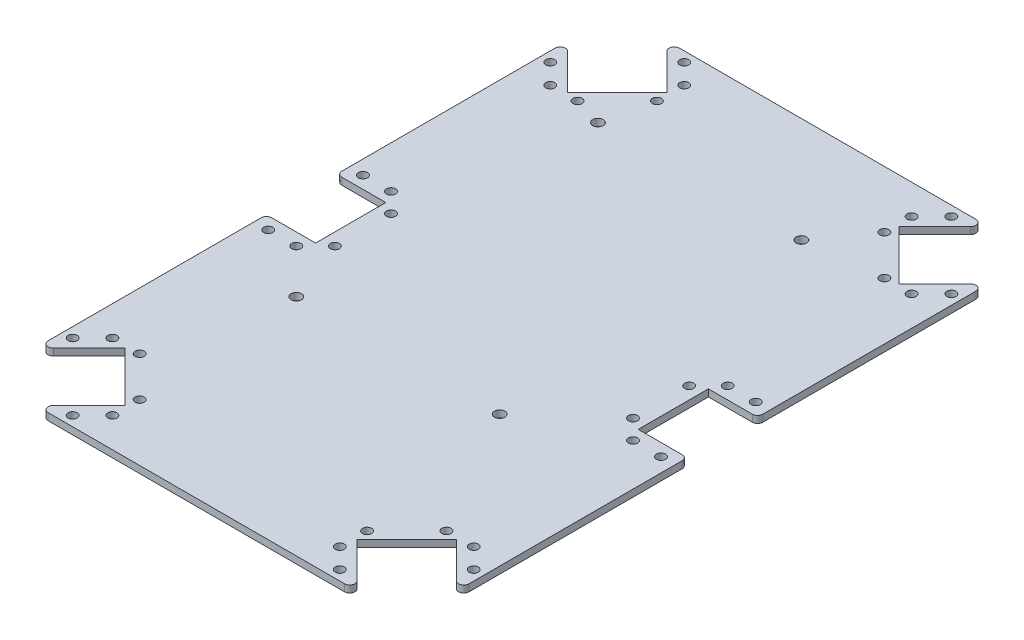
SolidWorks part; units mm, degrees
ref_plane "Front Plane" through (0, 0, 0) normal (0, 0, 1) x (1, 0, 0)
ref_plane "Top Plane" through (0, 0, 0) normal (0, 1, 0) x (1, 0, 0)
ref_plane "Right Plane" through (0, 0, 0) normal (1, 0, 0) x (0, 0, -1)
sketch "Sketch2" plane through (0, 0, 0) normal (0, 1, 0) x (1, 0, 0)
  line L0 (-60, 0) -> (60, 0) construction
  line L1 (-60, 90) -> (60, 90)
  line L2 (-60, 90) -> (-60, -90)
  line L3 (-60, -90) -> (60, -90)
  line L4 (60, 90) -> (60, -90)
  line L5 (60, 90) -> (0, 30) construction
  line L7 (0, 90) -> (0, -90) construction
  line L8 (32.4228, 73.7365) -> (28.5337, 77.6256) construction
  line L9 (28.5337, 77.6256) -> (32.4228, 81.5147) construction
  line L10 (32.4228, 81.5147) -> (38.0797, 87.1716) construction
  line L11 (38.0797, 87.1716) -> (40.9081, 90) construction
  circle A5 centre (32.4228, 73.7365) radius 1.3
  circle A6 centre (32.4228, 81.5147) radius 1.3
  circle A7 centre (38.0797, 87.1716) radius 1.3
  circle A8 centre (56, 13.5) radius 1.3
  circle A9 centre (48, 13.5) radius 1.3
  circle A10 centre (42.5, 8) radius 1.3
  circle A11 centre (42.5, -8) radius 1.3
  circle A12 centre (48, -13.5) radius 1.3
  circle A13 centre (56, -13.5) radius 1.3
  circle A14 centre (57.1716, 68.0797) radius 1.3
  circle A15 centre (51.5147, 62.4228) radius 1.3
  circle A16 centre (43.7365, 62.4228) radius 1.3
  circle A17 centre (57.1716, -68.0797) radius 1.3
  circle A18 centre (51.5147, -62.4228) radius 1.3
  circle A19 centre (43.7365, -62.4228) radius 1.3
  circle A20 centre (38.0797, -87.1716) radius 1.3
  circle A21 centre (32.4228, -81.5147) radius 1.3
  circle A22 centre (32.4228, -73.7365) radius 1.3
  circle A23 centre (-38.0797, 87.1716) radius 1.3
  circle A24 centre (-32.4228, 81.5147) radius 1.3
  circle A25 centre (-32.4228, 73.7365) radius 1.3
  circle A26 centre (-57.1716, 68.0797) radius 1.3
  circle A27 centre (-51.5147, 62.4228) radius 1.3
  circle A28 centre (-43.7365, 62.4228) radius 1.3
  circle A29 centre (-57.1716, -68.0797) radius 1.3
  circle A30 centre (-51.5147, -62.4228) radius 1.3
  circle A31 centre (-43.7365, -62.4228) radius 1.3
  circle A32 centre (-32.4228, -73.7365) radius 1.3
  circle A33 centre (-32.4228, -81.5147) radius 1.3
  circle A34 centre (-38.0797, -87.1716) radius 1.3
  circle A35 centre (-42.5, -8) radius 1.3
  circle A36 centre (-48, -13.5) radius 1.3
  circle A37 centre (-56, -13.5) radius 1.3
  circle A38 centre (-56, 13.5) radius 1.3
  circle A39 centre (-48, 13.5) radius 1.3
  circle A40 centre (-42.5, 8) radius 1.3
  point P0 (0, 0)
  point P27 (0, 0)
  dimension "D6" = 5.5
  dimension "D10" = 8
  dimension "D11" = 5.5
  dimension "D2" = 2.6
  dimension "D3" = 8
  dimension "D4" = 4
  dimension "D5" = 5.5
  dimension "D7" = 45
  dimension "D8" = 120
  dimension "D9" = 180
  dimension "D12" = 5.5
  dimension "D13" = 8
  dimension "D14" = 4
  dimension "D15" = 8
extrude "Boss-Extrude1" add sketch "Sketch2" along normal blind 2
sketch "Sketch3" plane through (0, 2, 0) normal (0, 1, 0) x (1, 0, 0)
  line L0 (0, -90) -> (0, 90) construction
  line L1 (-60, -90) -> (60, -90) construction
  line L2 (60, 90) -> (-60, 90) construction
  line L3 (-60, 0) -> (60, 0) construction
  line L4 (-60, 90) -> (-60, -90) construction
  line L5 (60, -90) -> (60, 90) construction
  line L6 (60, 90) -> (0, 30) construction
  line L7 (60, -10) -> (46, -10)
  line L8 (60, -10) -> (60, 10)
  line L9 (60, 10) -> (46, 10)
  line L10 (46, -10) -> (46, 10)
  line L11 (45.8579, 90) -> (33.1299, 77.2721)
  line L12 (33.1299, 77.2721) -> (47.2721, 63.1299)
  line L13 (47.2721, 63.1299) -> (60, 75.8579)
  line L14 (60, 75.8579) -> (60, 90)
  line L15 (60, 90) -> (45.8579, 90)
  line L16 (60, -75.8579) -> (60, -90)
  line L17 (47.2721, -63.1299) -> (60, -75.8579)
  line L18 (33.1299, -77.2721) -> (47.2721, -63.1299)
  line L19 (45.8579, -90) -> (33.1299, -77.2721)
  line L20 (60, -90) -> (45.8579, -90)
  line L21 (-60, 75.8579) -> (-60, 90)
  line L22 (-47.2721, 63.1299) -> (-60, 75.8579)
  line L23 (-33.1299, 77.2721) -> (-47.2721, 63.1299)
  line L24 (-45.8579, 90) -> (-33.1299, 77.2721)
  line L25 (-60, 90) -> (-45.8579, 90)
  line L26 (-60, 10) -> (-46, 10)
  line L27 (-46, -10) -> (-46, 10)
  line L28 (-60, -10) -> (-46, -10)
  line L29 (-60, -10) -> (-60, 10)
  line L30 (-47.2721, -63.1299) -> (-60, -75.8579)
  line L31 (-33.1299, -77.2721) -> (-47.2721, -63.1299)
  line L32 (-45.8579, -90) -> (-33.1299, -77.2721)
  line L33 (-60, -90) -> (-45.8579, -90)
  line L34 (-60, -75.8579) -> (-60, -90)
  dimension "D1" = 10
  dimension "D2" = 20
  dimension "D3" = 14
  dimension "D4" = 45
  dimension "D5" = 18
  dimension "D6" = 20
  dimension "D7" = 10
extrude "Cut-Extrude1" cut sketch "Sketch3" against normal up to surface (2 mm away) up to face at (0, 0, 0)
fillet "Fillet1" radius 1.5 12 edges at (-60, 1, 10) (-60, 1, -10) (-60, 1, 75.8579) (-45.8579, 1, 90) (45.8579, 1, 90) (60, 1, 75.8579) (60, 1, 10) (60, 1, -10) (60, 1, -75.8579) (45.8579, 1, -90) (-60, 1, -75.8579) (-45.8579, 1, -90)
sketch "Sketch4" plane through (0, 2, 0) normal (0, 1, 0) x (1, 0, 0)
  line L1 (-35.5, 60) -> (22.5, 60) construction
  line L2 (-35.5, 60) -> (-35.5, -26) construction
  line L3 (-35.5, -26) -> (22.5, -26) construction
  line L4 (22.5, 60) -> (22.5, -26) construction
  line L5 (-39.5, 70) -> (39.5, 70) construction
  line L6 (-39.5, 70) -> (-39.5, -30) construction
  line L7 (-39.5, -30) -> (39.5, -30) construction
  line L8 (39.5, 70) -> (39.5, -30) construction
  line L10 (-46, -10) -> (-46, 10) construction
  line L11 (46, 10) -> (46, -10) construction
  line L12 (42.2365, 90) -> (-42.2365, 90) construction
  circle A0 centre (-35.5, 60) radius 1.5
  circle A1 centre (22.5, 60) radius 1.5
  circle A2 centre (-35.5, -26) radius 1.5
  circle A3 centre (22.5, -26) radius 1.5
  point P12 (0, 0)
  point P13 (0, 0)
  dimension "D3" = 3
  dimension "D1" = 58
  dimension "D2" = 86
  dimension "D4" = 10
  dimension "D5" = 4
  dimension "D6" = 17
  dimension "D7" = 4
  dimension "D8" = 79
  dimension "D9" = 6.5
  dimension "D10" = 6.5
  dimension "D11" = 20
extrude "Cut-Extrude2" cut sketch "Sketch4" against normal up to surface (2 mm away) up to face at (0, 0, 0)
